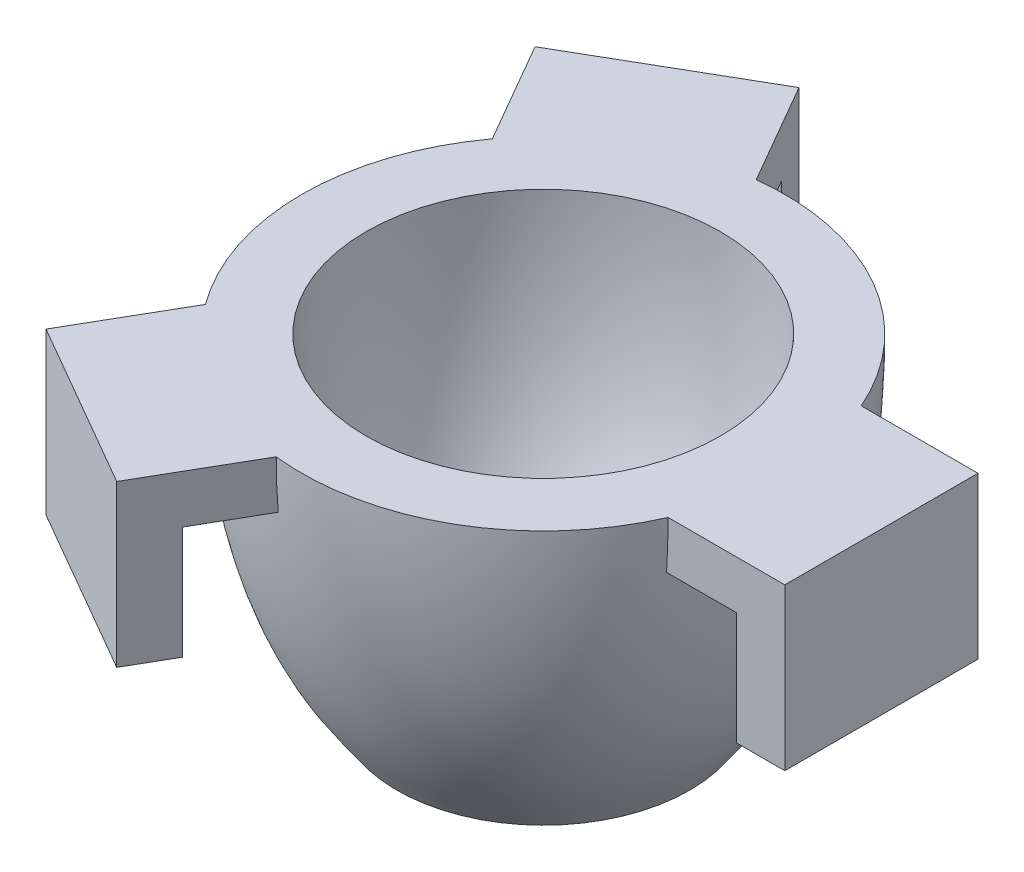
SolidWorks part; units mm, degrees
ref_plane "Front Plane" through (0, 0, 0) normal (0, 0, 1) x (1, 0, 0)
ref_plane "Top Plane" through (0, 0, 0) normal (0, 1, 0) x (1, 0, 0)
ref_plane "Right Plane" through (0, 0, 0) normal (1, 0, 0) x (0, 0, -1)
sketch "Sketch5" plane through (0, 0, 0) normal (0, 0, 1) x (1, 0, 0)
  line L0 (0, 0) -> (0, 8) construction
  line L1 (0, 8) -> (5.5, 8) construction
  line L2 (0, 0) -> (3.5, 0)
  line L3 (0, -2) -> (4.5486, -2)
  line L4 (0, -2) -> (0, 0)
  line L5 (5.5, 8) -> (7.5, 8)
  spline S0 degree 2 poles (3.5, 0) (5.5, 2.8924) (5.5, 8) knots 0 0 0 1 1 1
  spline S1 degree 1 poles (4.5486, -2) (7.5, 8) knots 0 0 1 1 construction
  spline S2 degree 2 poles (4.5486, -2) (4.7681, -1.6812) (5.1138, -1.1859) (5.4656, -0.6551) (5.8567, 0.0262) (6.3337, 1.0399) (6.8773, 2.5882) (7.5053, 5.6322) (7.5, 8) knots -0.1491 -0.1491 -0.1491 -0.041372 0.030447 0.102265 0.209994 0.353631 0.569087 1 1 1
  dimension "D1" = 3.5
  dimension "D2" = 5.5
  dimension "D3" = 4.5
  dimension "D4" = 8
  dimension "D6" = 2
revolve "Revolve1" add sketch "Sketch5" angle 360 about L0
sketch "Sketch6" plane through (0, 0, 0) normal (0, 0, 1) x (1, 0, 0)
  line L0 (10.5, 8) -> (5.5, 8)
  line L1 (10.5, 8) -> (10.5, 3)
  line L2 (10.5, 3) -> (9, 3)
  line L3 (9, 3) -> (9, 6.5)
  line L4 (5.5, 8) -> (5.5, 6.5)
  line L5 (5.5, 6.5) -> (9, 6.5)
  dimension "D1" = 1.5
  dimension "D2" = 5
  dimension "D3" = 5
extrude "Boss-Extrude1" add sketch "Sketch6" along normal blind 3 and the other way blind 3
pattern_circular "CirPattern1" count 3 over 360 about axis through (0, 8, 0) along (0, -1, 0) of "Boss-Extrude1"
sketch "Sketch7" plane through (0, 0, 0) normal (0, 1, 0) x (1, 0, 0)
  circle A0 centre (0, 0) radius 3.5
  circle A1 centre (0, 0) radius 3.5 construction
extrude "Cut-Extrude1" cut sketch "Sketch7" against normal through all
